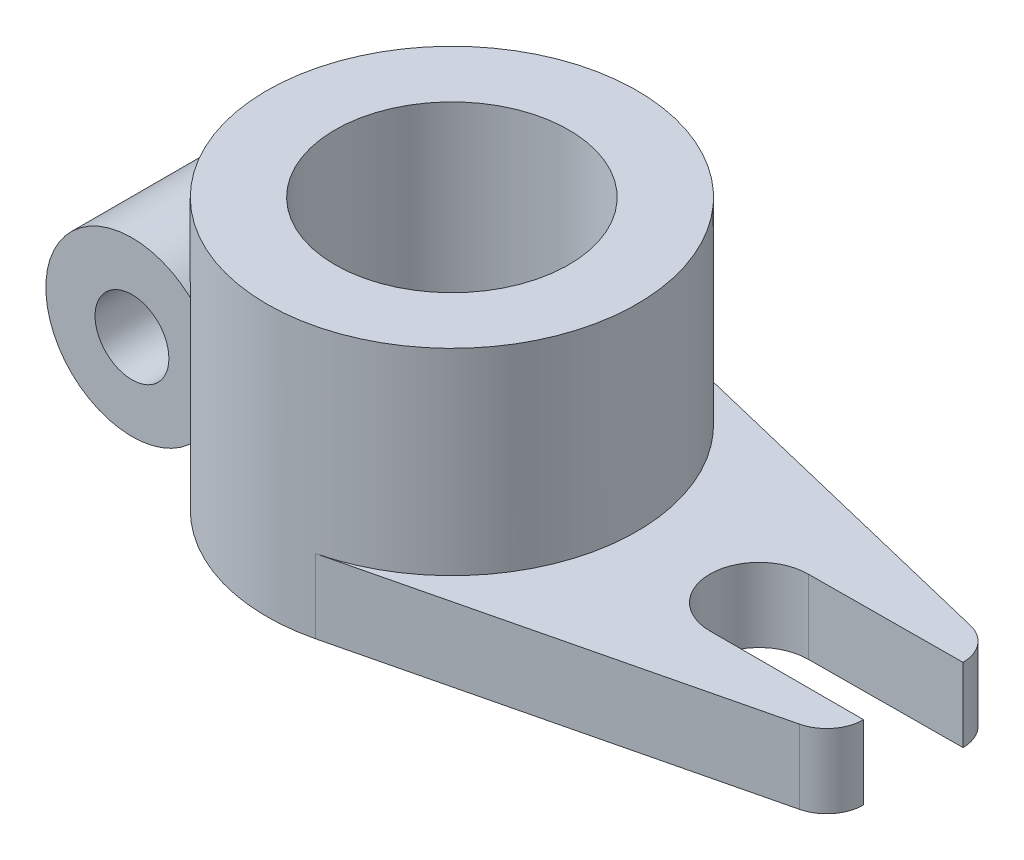
SolidWorks part; units mm, degrees
ref_plane "前视基准面" through (0, 0, 0) normal (0, 0, 1) x (1, 0, 0)
ref_plane "上视基准面" through (0, 0, 0) normal (0, 1, 0) x (1, 0, 0)
ref_plane "右视基准面" through (0, 0, 0) normal (1, 0, 0) x (0, 0, -1)
other "Configuration Table"
sketch "草图1" plane through (0, 0, 0) normal (0, 1, 0) x (1, 0, 0)
  line L2 (50, 8) -> (75, 8.1507)
  line L4 (7.0713, -29.1547) -> (70.4108, -13.8318)
  line L5 (7.0867, 29.3016) -> (70.4134, 13.9463)
  line L8 (50, -8) -> (75, -8)
  circle A0 centre (0, 0.0753) radius 30.0732
  circle A1 centre (0, 0.0753) radius 19
  arc A2 (50, 8) -> (50, -8) centre (50, 0) ccw
  arc A3 (70.4108, -13.8318) -> (75, -8) centre (69, -8) ccw
  arc A4 (75, 8.1507) -> (70.4134, 13.9463) centre (68.9993, 8.1145) ccw
extrude "凸台-拉伸1" add sketch "草图1" along normal blind 44 contours A0 A1 region at (22.9695, 0, -18.1408)
extrude "凸台-拉伸2" add sketch "草图1<3>" along normal blind 12 contours L2 A4 L5 A0 L4 A3 L8 A2 region at (41.1038, 0, 0)
sketch "草图1<3>" plane through (0, 0, 0) normal (0, 1, 0) x (1, 0, 0) same geometry as "草图1"
sketch "草图2" plane through (0, 0, 0) normal (0, 0, 1) x (1, 0, 0)
  line L3 (30.0732, 12) -> (30.0732, 44) construction
  circle A0 centre (-35.9268, 14.387) radius 14
  circle A1 centre (-35.9268, 14.387) radius 6
  dimension "D1" = 12
  dimension "D2" = 28
  dimension "D3" = 66
extrude "凸台-拉伸3" add sketch "草图2" along normal blind 16 and the other way blind 16
sketch "草图4" plane through (0, 0, 0) normal (1, 0, 0) x (0, 0, -1)
  line L0 (3.1485, 44) -> (3.1485, 0)
  line L1 (30.1485, 44) -> (-29.9979, 44) construction
  line L2 (-29.9979, 0) -> (30.1485, 0) construction
  line L3 (-2.9979, 44) -> (-2.9979, 0)
  line L4 (30.1485, 36) -> (-29.9979, 36)
  line L5 (30.1485, 0) -> (30.1485, 44) construction
  line L6 (-29.9979, 44) -> (-29.9979, 0) construction
  line L7 (30.1485, 8) -> (-29.9979, 8)
  dimension "D1" = 8
  dimension "D2" = 8
  dimension "D3" = 27
  dimension "D4" = 27
